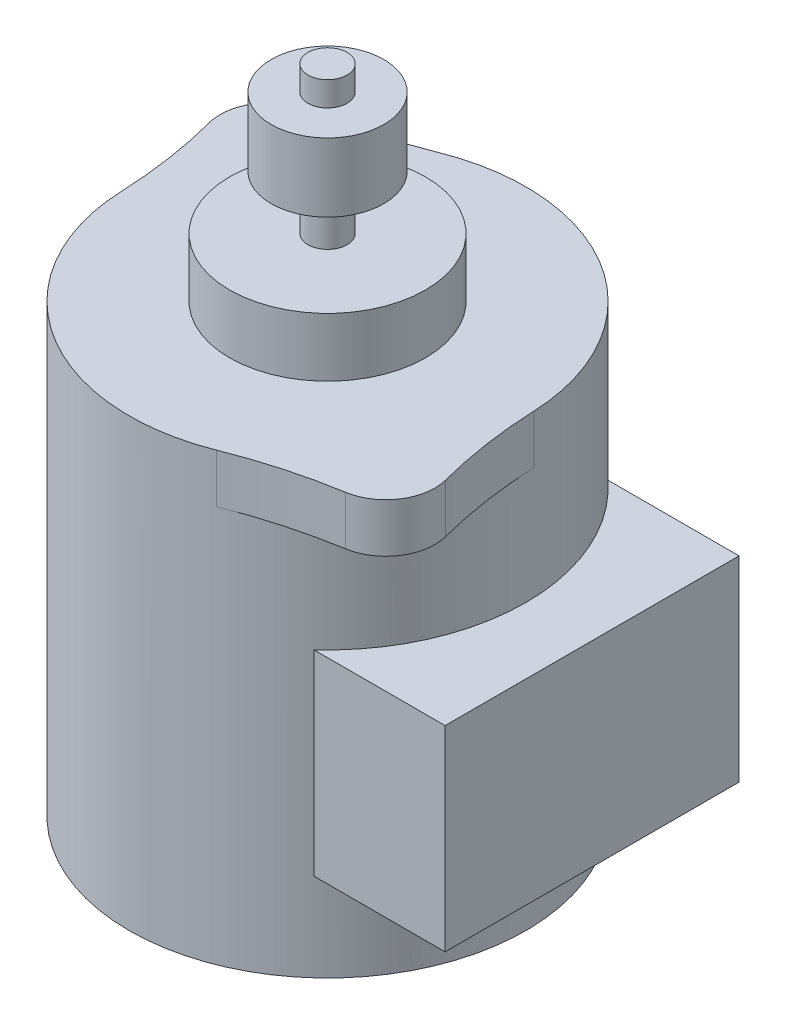
SolidWorks part; units mm, degrees
ref_plane "Front Plane" through (0, 0, 0) normal (0, 0, 1) x (1, 0, 0)
ref_plane "Top Plane" through (0, 0, 0) normal (0, 1, 0) x (1, 0, 0)
ref_plane "Right Plane" through (0, 0, 0) normal (1, 0, 0) x (0, 0, -1)
sketch "Sketch1" plane through (0, 0, 0) normal (0, 1, 0) x (1, 0, 0)
  circle A0 centre (0, 0) radius 4.05
  dimension "D1" = 8.1
extrude "Boss-Extrude1" add sketch "Sketch1" along normal blind 8.1
sketch "Sketch2" plane through (0, 8.1, 0) normal (0, 1, 0) x (1, 0, 0)
  line L0 (-3.3966, 2.2058) -> (3.3966, -2.2058) construction
  line L1 (-8.1053, 0) -> (8.1053, 0) construction
  arc A0 (-3.8335, 1.3063) -> (2.7526, -2.9708) centre (0, 0) ccw
  arc A1 (2.7526, -2.9708) -> (3.8335, -1.3063) centre (3.3966, -2.2058) ccw
  arc A2 (-2.7526, 2.9708) -> (-3.8335, 1.3063) centre (-3.3966, 2.2058) ccw
  circle A3 centre (0, 0) radius 4.05 construction
  arc A4 (3.8335, -1.3063) -> (-2.7526, 2.9708) centre (0, 0) ccw
  point P7 (0, 0)
  point P11 (0, 0)
  dimension "D1" = 8.1
  dimension "D2" = 2
  dimension "D3" = 33
extrude "Boss-Extrude2" add sketch "Sketch2" along normal blind 1
fillet "Fillet1" radius 10 4 edges at (2.7526, 8.6, 2.9708) (3.8335, 8.6, 1.3063) (-2.7526, 8.6, -2.9708) (-3.8335, 8.6, -1.3063)
sketch "Sketch3" plane through (0, 9.1, 0) normal (0, 1, 0) x (1, 0, 0)
  circle A0 centre (0, 0) radius 2
  dimension "D1" = 4
extrude "Boss-Extrude3" add sketch "Sketch3" along normal blind 1.2
sketch "Sketch4" plane through (0, 10.3, 0) normal (0, 1, 0) x (1, 0, 0)
  circle A0 centre (0, 0) radius 0.4
  dimension "D1" = 0.8
extrude "Boss-Extrude4" add sketch "Sketch4" along normal blind 3
sketch "Sketch5" plane through (0, 13.3, 0) normal (0, 1, 0) x (1, 0, 0)
  circle A0 centre (0, 0) radius 1.15
  dimension "D1" = 2.3
extrude "Boss-Extrude5" add sketch "Sketch5" against normal blind 1.4 from offset 0.5 offset against normal yes
ref_plane "Plane1" through (5.4, 0, 0) normal (1, 0, 0) x (0, 0, -1)
sketch "Sketch6" plane through (5.4, 0, 0) normal (1, 0, 0) x (0, 0, -1)
  line L1 (-3, 1.8) -> (3, 1.8)
  line L2 (-3, 1.8) -> (-3, 5.8)
  line L3 (-3, 5.8) -> (3, 5.8)
  line L4 (3, 1.8) -> (3, 5.8)
  line L5 (-3, 1.8) -> (3, 5.8) construction
  line L6 (-3, 5.8) -> (3, 1.8) construction
  point P0 (0, 3.8)
  dimension "D1" = 4
  dimension "D2" = 6
  dimension "D3" = 1.8
extrude "Boss-Extrude6" add sketch "Sketch6" against normal up to next
